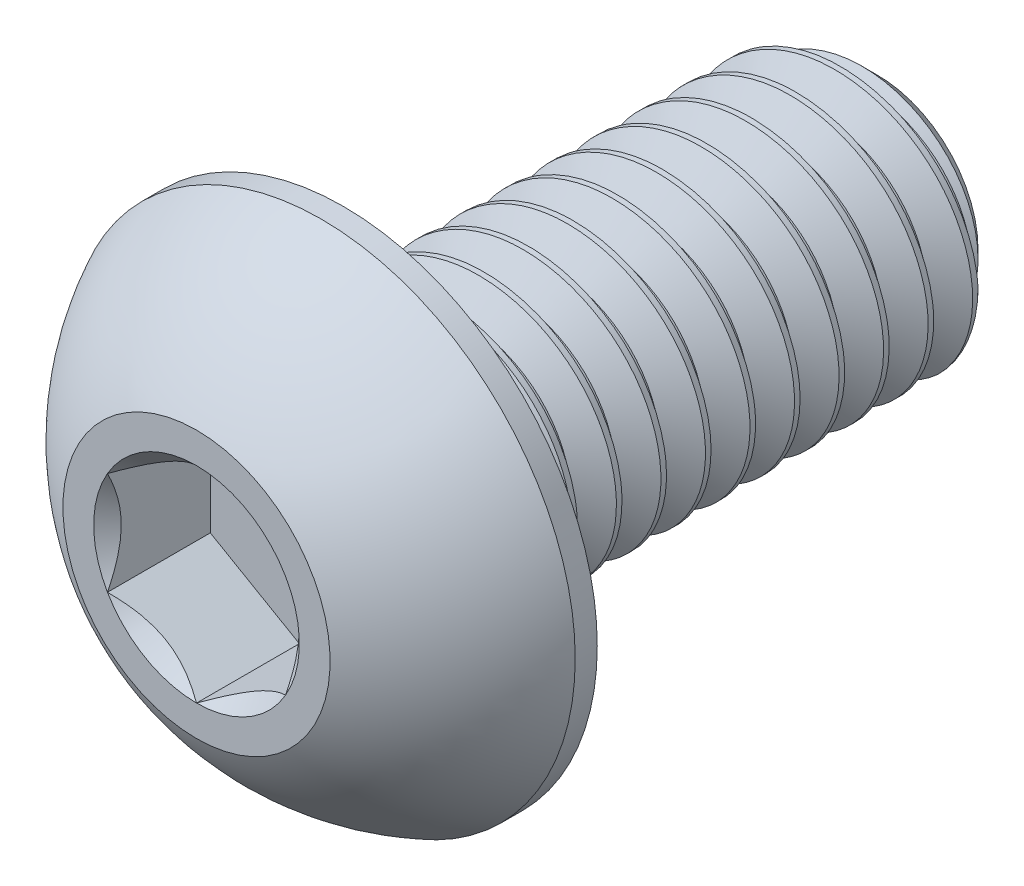
SolidWorks part; units mm, degrees
ref_plane "Front" through (0, 0, 0) normal (0, 0, 1) x (1, 0, 0)
ref_plane "Top" through (0, 0, 0) normal (0, 1, 0) x (1, 0, 0)
ref_plane "Right" through (0, 0, 0) normal (1, 0, 0) x (0, 0, -1)
sketch "Sketch1" plane through (0, 0, 0) normal (1, 0, 0) x (0, 0, -1)
  line L2 (1.65, 1.5) -> (7.65, 1.5)
  line L3 (7.65, 1.5) -> (7.65, 0)
  line L4 (7.65, 0) -> (1.65, 0)
  line L6 (1.4025, 2.85) -> (1.65, 2.85) construction
  line L7 (7.65, 1.5) -> (7.65, -1.5) construction
  line L8 (0, 0) -> (1.65, 0) construction
  line L9 (1.65, 2.85) -> (1.65, -2.85) construction
  line L11 (1.65, 1.5) -> (1.65, 0)
  line L13 (0, 1) -> (0, -1) construction
  line L14 (0, 1) -> (0, 1.5) construction
  line L15 (7.6187, 1.5541) -> (7.8687, 1.1211) construction
  line L16 (7.8687, 1.1211) -> (8.1187, 1.5541) construction
  line L17 (8.1187, 1.5541) -> (7.6187, 1.5541) construction
  line L18 (7.65, 1.5) -> (8.0875, 1.5) construction
  line L19 (7.8687, 1.5541) -> (7.8687, 1.5) construction
  line L20 (7.8687, 1.5) -> (7.8687, 1.1752) construction
  line L21 (7.8687, 1.1752) -> (7.8687, 1.1211) construction
  line L22 (7.8375, 1.1752) -> (7.9, 1.1752)
  line L23 (7.6344, 1.5271) -> (8.1031, 1.5271)
  line L24 (7.9, 1.1752) -> (8.1031, 1.5271)
  line L25 (7.8375, 1.1752) -> (7.6344, 1.5271)
  line L26 (7.275, 1.5) -> (7.65, 1.125)
  arc A3 (0, 1.5) -> (1.4025, 2.85) centre (2.7948, 0) cw construction
  point P29 (7.8687, 1.5271)
  point P30 (6.4, -1.5)
  dimension "D1" = 0.2475
  dimension "Pitch" = 0.5
  dimension "D3" = 0.0625
  dimension "D2" = 0.375
  dimension "D4" = 45
  dimension "D5" = 1.25
sketch "Sketch10" plane through (0, 0, 0) normal (1, 0, 0) x (0, 0, -1)
  line L0 (7.275, 1.5) -> (7.65, 1.125) construction
  line L1 (7.275, 1.5) -> (7.65, 1.125)
  line L4 (7.65, 1.5) -> (1.65, 1.5)
  line L5 (7.65, 0) -> (7.65, 1.5)
  line L6 (1.65, 0) -> (7.65, 0)
  line L7 (1.65, 1.5) -> (1.65, 0)
  line L8 (7.275, 1.5) -> (1.65, 1.5)
  line L9 (7.65, 0) -> (7.65, 1.125)
  line L10 (1.65, 0) -> (7.65, 0)
  line L11 (1.65, 1.5) -> (1.65, 0)
  dimension "D1" = 0
revolve "Revolve3" add sketch "Sketch10" angle 360 about L8
sketch "Sketch7" plane through (0, 0, 0) normal (1, 0, 0) x (0, 0, -1)
  line L6 (1.4025, 2.85) -> (1.65, 2.85) construction
  line L8 (0, 0) -> (1.65, 0) construction
  line L11 (1.65, 2.85) -> (1.65, -2.85) construction
  line L12 (1.4025, 2.85) -> (1.65, 2.85)
  line L13 (0, 0) -> (1.65, 0)
  line L14 (0, 1) -> (0, -1) construction
  line L15 (1.65, 2.85) -> (1.65, 0)
  line L16 (0, 1.5) -> (0, 0)
  arc A2 (1.4025, 2.85) -> (0, 1.5) centre (2.7948, 0) ccw construction
  arc A3 (1.4025, 2.85) -> (0, 1.5) centre (2.7948, 0) ccw
revolve "Revolve2" add sketch "Sketch7" angle 360 mid plane about L13
sketch "Sketch5" plane through (0, 0, 0) normal (0, 0, 1) x (1, 0, 0)
  line L1 (1, -0.5774) -> (1, 0.5774)
  line L2 (1, 0.5774) -> (0, 1.1547)
  line L3 (0, 1.1547) -> (-1, 0.5774)
  line L4 (-1, 0.5774) -> (-1, -0.5774)
  line L5 (-1, -0.5774) -> (0, -1.1547)
  line L6 (0, -1.1547) -> (1, -0.5774)
  circle A0 centre (0, 0) radius 1 construction
extrude "Cut-Extrude2" cut sketch "Sketch5" against normal blind 1.155
sketch "Sketch6" plane through (0, 0, 0) normal (0, 0, 1) x (1, 0, 0)
  circle A0 centre (0, 0) radius 1.1547
extrude "Cut-Extrude3" cut sketch "Sketch6" against normal blind 1.155 draft 45
sketch "Sketch9" plane through (0, 0, -1.65) normal (0, 0, -1) x (-1, 0, 0)
  circle A0 centre (0, 0) radius 1.5 construction
  circle A4 centre (0, 0) radius 1.5
split "Split1" bodies to split 113 resulting bodies 123 124 split by face at (2.85, 0, -1.65)
sketch "Sketch11" plane through (0, 0, -7.65) normal (0, 0, -1) x (-1, 0, 0)
  circle A0 centre (0, 0) radius 1.5 construction
  circle A1 centre (0, 0) radius 1.5
curve "Helix/Spiral1" pitch 0.5 height 7.65 radius 1.5 centre (0, 0, -7.65) axis (0, 0, 1) start towards (0, 1, 0)
sketch "Sketch12" plane through (0, 0, 0) normal (1, 0, 0) x (0, 0, -1)
  line L0 (7.8375, 1.1752) -> (7.9, 1.1752) construction
  line L1 (7.9, 1.1752) -> (8.1031, 1.5271) construction
  line L2 (7.6344, 1.5271) -> (8.1031, 1.5271) construction
  line L3 (7.8375, 1.1752) -> (7.6344, 1.5271) construction
  line L4 (7.8375, 1.1752) -> (7.9, 1.1752)
  line L5 (7.9, 1.1752) -> (8.1031, 1.5271)
  line L6 (7.6344, 1.5271) -> (8.1031, 1.5271)
  line L7 (7.8375, 1.1752) -> (7.6344, 1.5271)
sweep "Cut-Sweep2" cut profiles "Sketch12" path "Helix/Spiral1" align with end faces yes
extrude "Boss-Extrude1" add sketch "Sketch9" along normal blind 10 draft 45
equation "\"D1@Cut-Extrude2\" = \"Head Ht@Sketch1\" * .7"
equation "\"D1@Sketch1\" = \"Head Ht@Sketch1\" * .15"
equation "\"D1@Cut-Extrude3\" = \"D1@Cut-Extrude2\""
equation "\"D3@Sketch1\" = \"Pitch@Sketch1\" / 8"
equation "\"D2@Sketch1\"=\"Pitch@Sketch1\"*0.75"
equation "\"D3@Helix/Spiral1\" = \"Lg@Sketch1\" + \"Head Ht@Sketch1\""
equation "\"D4@Helix/Spiral1\"=\"pitch@sketch1\""
equation "\"D5@Sketch1\"=\"Pitch@Sketch1\"*2.5"
